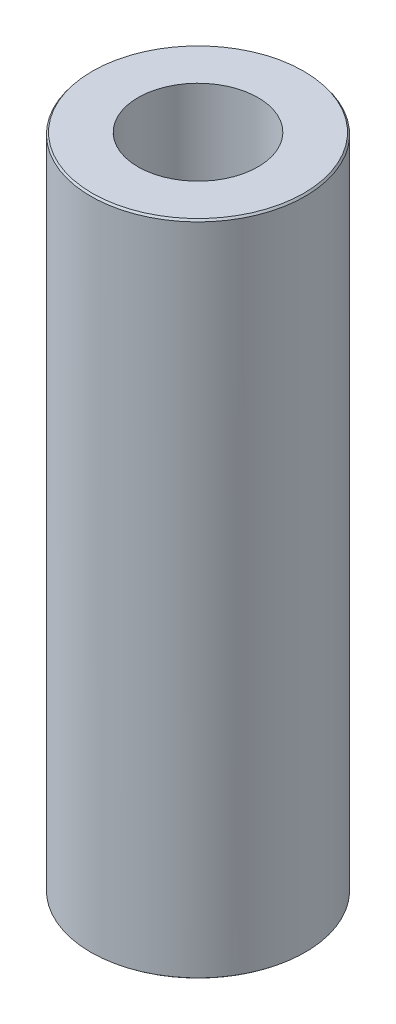
SolidWorks part; units mm, degrees
ref_plane "Front Plane" through (0, 0, 0) normal (0, 0, 1) x (1, 0, 0)
ref_plane "Top Plane" through (0, 0, 0) normal (0, 1, 0) x (1, 0, 0)
ref_plane "Right Plane" through (0, 0, 0) normal (1, 0, 0) x (0, 0, -1)
sketch "Sketch1" plane through (0, 0, 0) normal (0, 1, 0) x (1, 0, 0)
  circle A0 centre (0, 0) radius 47.5
  dimension "SHAFT_OD" = 95
extrude "Boss-Extrude1" add sketch "Sketch1" along normal blind 291.5304
sketch "Sketch2" plane through (0, 0, 0) normal (0, 1, 0) x (1, 0, 0)
  circle A0 centre (0, 0) radius 26.5882
  dimension "BORE_D" = 53.1764
extrude "Cut-Extrude1" cut sketch "Sketch2" along normal through all
chamfer "Chamfer1" distance 0.8389 angle 38.043 2 edges at (0, 291.5304, 47.5) (0, 0, 47.5) first distance on face at (0, 291.5304, 47.5) first distance on face at (0, 0, 26.5882)
